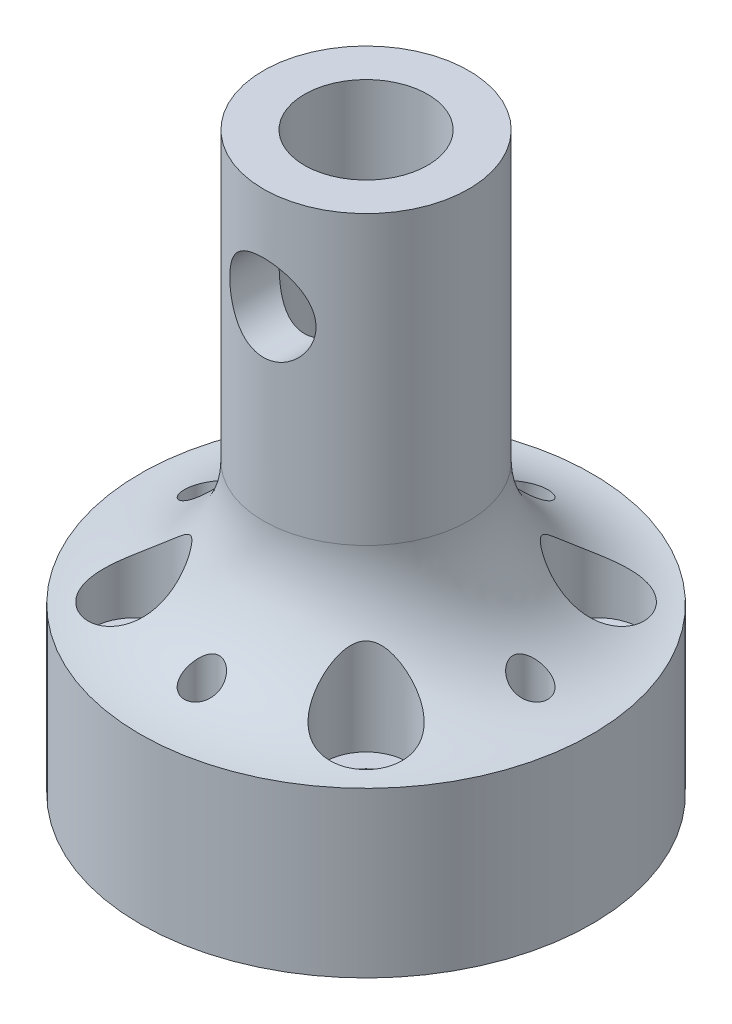
SolidWorks part; units mm, degrees
ref_plane "Front" through (0, 0, 0) normal (0, 0, 1) x (1, 0, 0)
ref_plane "Top" through (0, 0, 0) normal (0, 1, 0) x (1, 0, 0)
ref_plane "Right" through (0, 0, 0) normal (1, 0, 0) x (0, 0, -1)
sketch "Sketch1" plane through (0, 0, 0) normal (0, 1, 0) x (1, 0, 0)
  line L0 (0, 0) -> (-5.6569, 5.6569) construction
  line L1 (-5.6569, 5.6569) -> (0, 8) construction
  line L2 (-5.6569, 5.6569) -> (-8, 0) construction
  line L3 (5.6569, 5.6569) -> (8, 0) construction
  line L4 (5.6569, -5.6569) -> (0, -8) construction
  line L5 (-5.6569, -5.6569) -> (-8, 0) construction
  circle A0 centre (0, 0) radius 11
  circle A1 centre (0, 0) radius 8 construction
  circle A2 centre (0, 8) radius 0.85
  circle A3 centre (-5.6569, 5.6569) radius 1
  circle A4 centre (8, 0) radius 0.85
  circle A5 centre (5.6569, 5.6569) radius 1
  circle A6 centre (0, -8) radius 0.85
  circle A7 centre (5.6569, -5.6569) radius 1
  circle A8 centre (-8, 0) radius 0.85
  circle A9 centre (-5.6569, -5.6569) radius 1
  point P24 (0, 0)
  dimension "D1" = 22
  dimension "D2" = 16
  dimension "D3" = 1.7
  dimension "D4" = 2
  dimension "D5" = 4
extrude "Boss-Extrude1" add sketch "Sketch1" along normal blind 8
sketch "Sketch2" plane through (0, 8, 0) normal (0, 1, 0) x (1, 0, 0)
  circle A0 centre (-5.6569, 5.6569) radius 2
  circle A1 centre (5.6569, 5.6569) radius 2
  circle A2 centre (5.6569, -5.6569) radius 2
  circle A3 centre (-5.6569, -5.6569) radius 2
  point P12 (0, 0)
  dimension "D1" = 4
  dimension "D2" = 4
extrude "Cut-Extrude1" cut sketch "Sketch2" against normal blind 2
chamfer "Chamfer1" [suppressed] distance 0.5 angle 45
sketch "Sketch3" plane through (0, 8, 0) normal (0, 1, 0) x (1, 0, 0)
  circle A0 centre (0, 0) radius 5
  dimension "D1" = 10
extrude "Boss-Extrude2" add sketch "Sketch3" along normal blind 20
sketch "Sketch5" plane through (0, 28, 0) normal (0, 1, 0) x (1, 0, 0)
  circle A0 centre (0, 0) radius 3
  dimension "D1" = 6
extrude "Cut-Extrude2" cut sketch "Sketch5" against normal through all
sketch "Sketch6" plane through (0, 0, 0) normal (0, 0, 1) x (1, 0, 0)
  line L0 (0, -50) -> (0, 50) construction
  line L1 (3, 28) -> (-3, 28) construction
  circle A0 centre (0, 23) radius 2.5
  dimension "D1" = 5
  dimension "D2" = 5
hole_wizard "Tap Drill for M5x0.8 Tap1" positions "Sketch7" profile "Sketch8" hole size "M5x0.8" standard "ANSI Metric" end condition up to next
sketch "Sketch7" plane through (0, 0, 0) normal (0, 0, 1) x (1, 0, 0)
  point P0 (0, 23)
sketch "Sketch8" plane through (0, 23, 0) normal (1, 0, 0) x (0, 1, 0)
  line L0 (0, 0) -> (0, 5)
  line L1 (0, 5) -> (2.1, 5)
  line L2 (2.1, 5) -> (2.1, 0)
  line L5 (2.1, 0) -> (0, 0)
  line L11 (0, -6.35) -> (0, 107.95) construction
  dimension "Thru Hole Dia." = 4.2
  dimension "Thru Hole Depth" = 5
fillet "Fillet1" radius 6 1 edges at (0, 8, 5)
